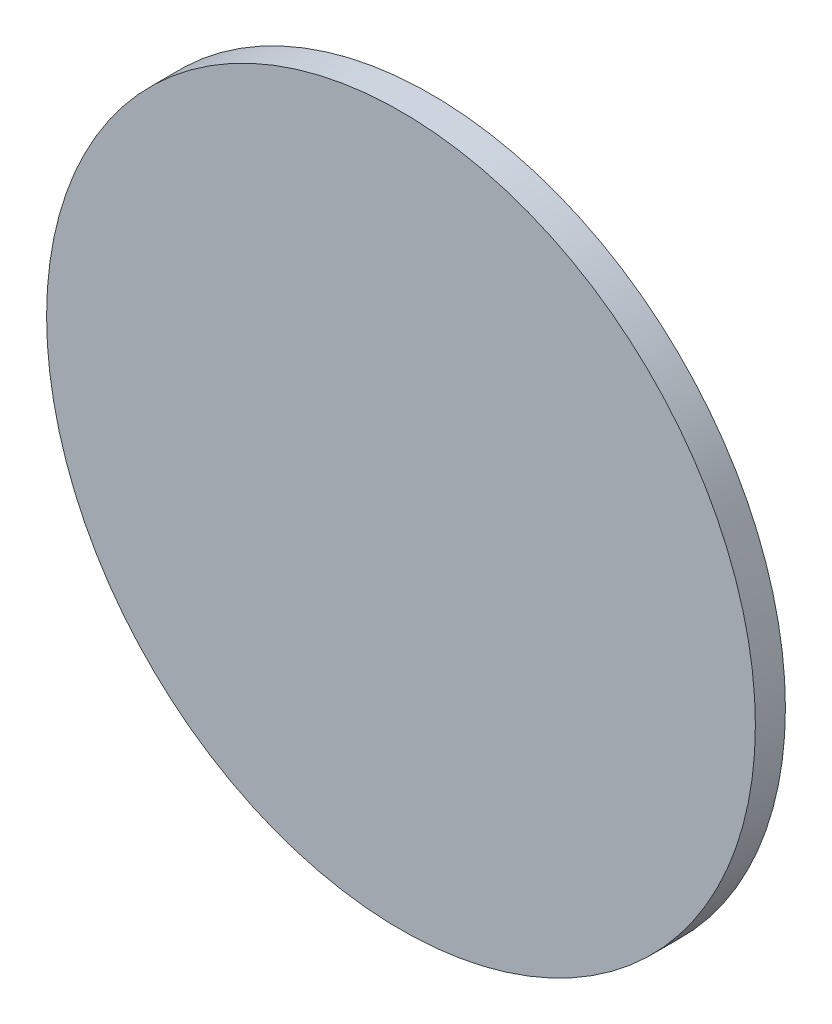
SolidWorks part; units mm, degrees
ref_plane "Front Plane" through (0, 0, 0) normal (0, 0, 1) x (1, 0, 0)
ref_plane "Top Plane" through (0, 0, 0) normal (0, 1, 0) x (1, 0, 0)
ref_plane "Right Plane" through (0, 0, 0) normal (1, 0, 0) x (0, 0, -1)
sketch "Sketch1" plane through (0, 0, 0) normal (0, 0, 1) x (1, 0, 0)
  circle A0 centre (0, 0) radius 37.465
  dimension "D1" = 74.93
extrude "Boss-Extrude1" add sketch "Sketch1" along normal blind 3.175
